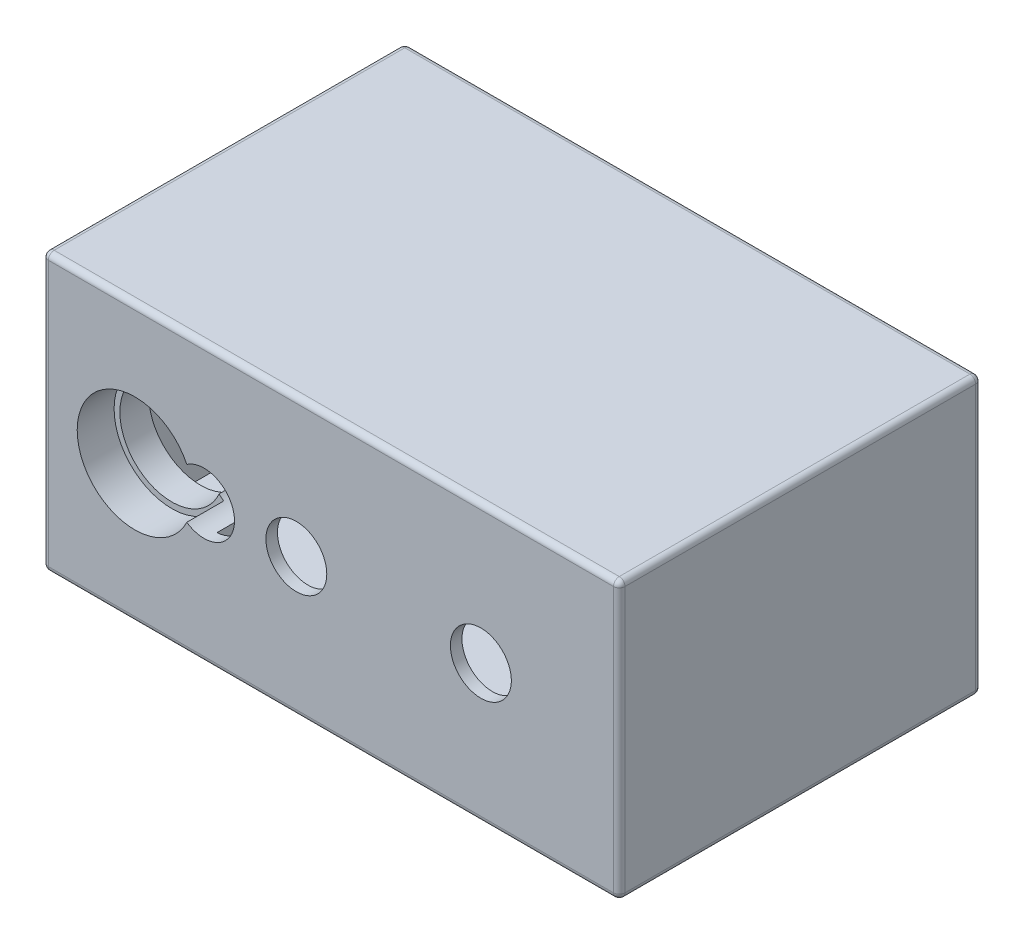
SolidWorks part; units mm, degrees
material "1060 Alloy"
ref_plane "Front Plane" through (0, 0, 0) normal (0, 0, 1) x (1, 0, 0)
ref_plane "Top Plane" through (0, 0, 0) normal (0, 1, 0) x (1, 0, 0)
ref_plane "Right Plane" through (0, 0, 0) normal (1, 0, 0) x (0, 0, -1)
sketch "Sketch1" plane through (0, 0, 0) normal (0, 0, 1) x (1, 0, 0)
  line L1 (-25.4, 38.1) -> (133.35, 38.1)
  line L2 (-25.4, 38.1) -> (-25.4, -38.1)
  line L3 (-25.4, -38.1) -> (133.35, -38.1)
  line L4 (133.35, 38.1) -> (133.35, -38.1)
  circle A1 centre (0, 0) radius 8.382
  circle A4 centre (19.05, 0) radius 8.382
  circle A5 centre (44.45, 0) radius 8.382
  point P14 (-25.4, 0)
  dimension "D1" = 76.2
  dimension "D2" = 16.764
  dimension "D3" = 16.764
  dimension "D4" = 19.05
  dimension "D6" = 16.764
  dimension "D5" = 158.75
  dimension "D7" = 25.4
  dimension "D10" = 25.4
extrude "Boss-Extrude1" add sketch "Sketch1" along normal blind 3.175
sketch "Sketch2" plane through (0, 0, 3.175) normal (0, 0, 1) x (1, 0, 0)
  line L0 (133.35, 38.1) -> (-25.4, 38.1) construction
  line L1 (-25.4, -38.1) -> (-22.225, -38.1)
  line L2 (-25.4, -38.1) -> (-25.4, 38.1)
  line L3 (-25.4, 38.1) -> (-22.225, 38.1)
  line L4 (-22.225, -38.1) -> (-22.225, 38.1)
  line L6 (133.35, -38.1) -> (130.175, -38.1)
  line L7 (133.35, -38.1) -> (133.35, 38.1)
  line L8 (133.35, 38.1) -> (130.175, 38.1)
  line L9 (130.175, -38.1) -> (130.175, 38.1)
  dimension "D1" = 3.175
  dimension "D2" = 3.175
extrude "Boss-Extrude2" add sketch "Sketch2" along normal blind 96.52
sketch "Sketch5" plane through (0, 38.1, 0) normal (0, 1, 0) x (1, 0, 0)
  line L0 (-22.225, -84.7725) -> (16.2719, -84.7725)
  line L1 (-22.225, -99.695) -> (-22.225, -3.175) construction
  line L2 (16.2719, -84.7725) -> (16.2719, -99.695)
  line L4 (16.2719, -99.695) -> (130.175, -99.695)
  line L5 (-25.4, -99.695) -> (-25.4, 0) construction
  line L6 (-22.225, -81.5975) -> (19.4469, -81.5975)
  line L7 (19.4469, -81.5975) -> (19.4469, -96.52)
  line L8 (19.4469, -96.52) -> (130.175, -96.52)
  line L9 (-22.225, -81.5975) -> (-22.225, -84.7725)
  line L10 (130.175, -96.52) -> (130.175, -99.695)
  line L11 (16.2719, -99.695) -> (-22.225, -99.695)
  line L12 (-22.225, -99.695) -> (-22.225, -84.7725)
  line L13 (16.2719, -84.7725) -> (16.2719, -99.695)
  line M4 (-22.225, -99.695) -> (-22.225, -3.175)
  line M6 (130.175, -3.175) -> (130.175, -99.695)
  dimension "D1" = 41.6719
  dimension "D2" = 14.9225
  dimension "D3" = 3.175
extrude "Boss-Extrude4" add sketch "Sketch5" against normal up to surface (76.2 mm away) contours L11 L2 L0 M4 | L8 L7 L6 L0 L2 L4 M4 M6 region at (-20.6903, 38.1, 83.185) region at (-2.9766, 38.1, 92.2338) up to face at (53.975, -38.1, 50.6412)
sketch "Sketch10" plane through (0, 0, 99.695) normal (0, 0, 1) x (1, 0, 0)
  circle A0 centre (0, 0) radius 15.875
  circle A1 centre (19.05, 0) radius 8.382
  circle A2 centre (44.45, 0) radius 8.382
  dimension "D1" = 31.75
  dimension "D2" = 16.764
  dimension "D3" = 16.764
  dimension "D5" = 19.05
  dimension "D6" = 25.4
extrude "Cut-Extrude3" cut sketch "Sketch10" against normal up to next contours A0 A1 | A2 | A1 region at (20.6876, 0, 99.695) region at (44.45, 0, 99.695)
extrude "Cut-Extrude4" cut sketch "Sketch10<3>" against normal blind 10.16 contours A1 A0 region at (-0.903, 0, 99.695)
sketch "Sketch10<3>" plane through (0, 0, 99.695) normal (0, 0, 1) x (1, 0, 0) same geometry as "Sketch10"
sketch "Sketch11" plane through (0, 0, 89.535) normal (0, 0, 1) x (1, 0, 0)
  circle A0 centre (0, 0) radius 14.2875
  dimension "D1" = 28.575
extrude "Cut-Extrude5" cut sketch "Sketch11" against normal up to next
sketch "Sketch12" plane through (0, 0, 0) normal (0, 0, -1) x (-1, 0, 0)
  line L0 (-133.35, -38.1) -> (-133.35, 38.1) construction
  circle A0 centre (-95.25, 0) radius 8.382
  dimension "D1" = 16.764
  dimension "D2" = 38.1
extrude "Cut-Extrude6" cut sketch "Sketch12" against normal through all
sketch "Sketch13" plane through (133.35, 0, 0) normal (1, 0, 0) x (0, 0, -1)
  line L0 (0, -38.1) -> (0, 38.1) construction
  line L1 (-99.695, -38.1) -> (0, -38.1)
  line L2 (-99.695, -38.1) -> (-99.695, -34.925)
  line L3 (-99.695, -34.925) -> (0, -34.925)
  line L4 (0, -38.1) -> (0, -34.925)
  line L5 (-99.695, -38.1) -> (-99.695, 38.1) construction
  line L6 (0, 38.1) -> (-99.695, 38.1)
  line L7 (0, 38.1) -> (0, 34.925)
  line L8 (0, 34.925) -> (-99.695, 34.925)
  line L9 (-99.695, 38.1) -> (-99.695, 34.925)
  dimension "D1" = 3.175
  dimension "D2" = 3.175
extrude "Boss-Extrude5" add sketch "Sketch13" against normal up to surface (158.75 mm away) up to face at (-25.4, 0, 49.8475)
fillet "Fillet1" radius 1.5875 12 edges at (133.35, 38.1, 49.8475) (53.975, 38.1, 99.695) (133.35, 0, 0) (53.975, 38.1, 0) (-25.4, 0, 0) (-25.4, 38.1, 49.8475) (-25.4, 0, 99.695) (-25.4, -38.1, 49.8475) (53.975, -38.1, 99.695) (133.35, -38.1, 49.8475) (53.975, -38.1, 0) (133.35, 0, 99.695)
